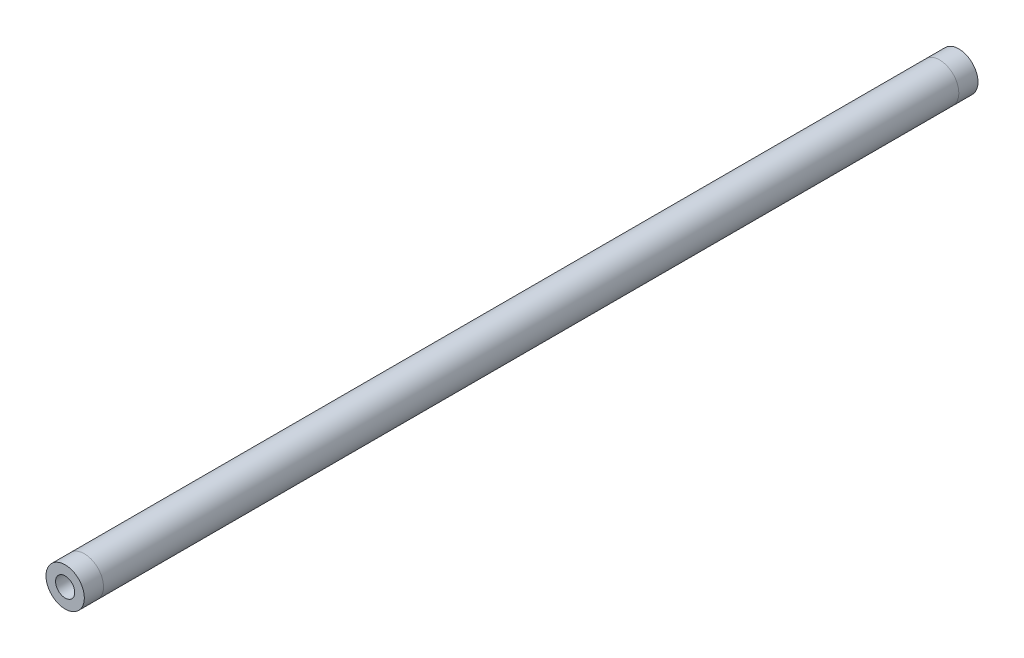
SolidWorks part; units mm, degrees
material "AISI 4130 Steel, normalized at 870C"
ref_plane "Front Plane" through (0, 0, 0) normal (0, 0, 1) x (1, 0, 0)
ref_plane "Top Plane" through (0, 0, 0) normal (0, 1, 0) x (1, 0, 0)
ref_plane "Right Plane" through (0, 0, 0) normal (1, 0, 0) x (0, 0, -1)
sketch "Axis" plane through (0, 0, 0) normal (0, 1, 0) x (1, 0, 0)
  line L0 (0, 0) -> (0, 21.9075) construction
  line L1 (0, 21.9075) -> (0, 317.7011) construction
  line L2 (0, 317.7011) -> (0, 339.6086) construction
  dimension "D1" = 21.9075
  dimension "D2" = 339.6086
sketch "Sketch2" plane through (0, 0, 0) normal (0, 0, 1) x (1, 0, 0)
  circle A0 centre (0, 0) radius 6.35
  circle A1 centre (0, 0) radius 3.175
  circle A2 centre (0, 0) radius 5.461
  dimension "D1" = 12.7
  dimension "D2" = 6.35
  dimension "D3" = 10.922
extrude "Threaded Insert 1-1" add sketch "Sketch2" against normal blind 6.35 from vertex contours A0 A2 | A2 A1 region at (-6.1704, 0, 0) region at (-5.3065, 0, 0) starting at point (0, 0, -21.9075)
extrude "Threaded Insert 1-2" add sketch "Sketch2<5>" against normal blind 6.35 from surface contours A2 A1 region at (-5.3065, 0, 0) starting at face at (6.35, 0, -28.2575)
sketch "Sketch2<5>" plane through (0, 0, 0) normal (0, 0, 1) x (1, 0, 0) same geometry as "Sketch2"
extrude "Boss-Extrude4" add sketch "Sketch2<7>" along normal blind 6.35 from vertex separate body contours A0 A2 | A2 A1 region at (-6.1704, 0, 0) region at (-5.3065, 0, 0) starting at point (0, 0, -317.7011)
sketch "Sketch2<7>" plane through (0, 0, 0) normal (0, 0, 1) x (1, 0, 0) same geometry as "Sketch2"
extrude "Boss-Extrude5" add sketch "Sketch2<8>" along normal blind 6.35 from surface contours A2 A1 region at (-5.3065, 0, 0) starting at face at (6.35, 0, -311.3511)
sketch "Sketch2<8>" plane through (0, 0, 0) normal (0, 0, 1) x (1, 0, 0) same geometry as "Sketch2"
extrude "Boss-Extrude6" add sketch "Sketch2<9>" against normal up to surface (311.3511 mm away) from surface separate body contours A0 A2 region at (-6.1704, 0, 0) up to face at (5.461, 0, -311.3511) starting at face at (5.461, 0, -28.2575)
sketch "Sketch2<9>" plane through (0, 0, 0) normal (0, 0, 1) x (1, 0, 0) same geometry as "Sketch2"
move or copy body "Body-Move/Copy1" [suppressed] bodies to move or copy 102 105 106 parameters "D1"=0, "D2"=0, "D3"=0
equation "\"Tube Outer Diameter\"= .5"
equation "\"Tube Inner Diameter\" = .430"
equation "\"Rod end Diameter\"= .25"
equation "\"Threaded Insert Out\"= .25"
equation "\"Threaded Insert In\"= .25'`"
equation "\"D1@Sketch2\"=\"Tube Outer Diameter\""
equation "\"D2@Sketch2\"=\"Rod end Diameter\""
equation "\"D1@Threaded Insert 1-1\" = \"Threaded Insert Out\""
equation "\"D3@Sketch2\"=\"Tube Inner Diameter\""
equation "\"D1@Threaded Insert 1-2\" = \"Threaded Insert In\""
equation "\"D1@Boss-Extrude4\"=\"Threaded Insert Out\""
equation "\"D1@Boss-Extrude5\"=\"Threaded Insert In\""
